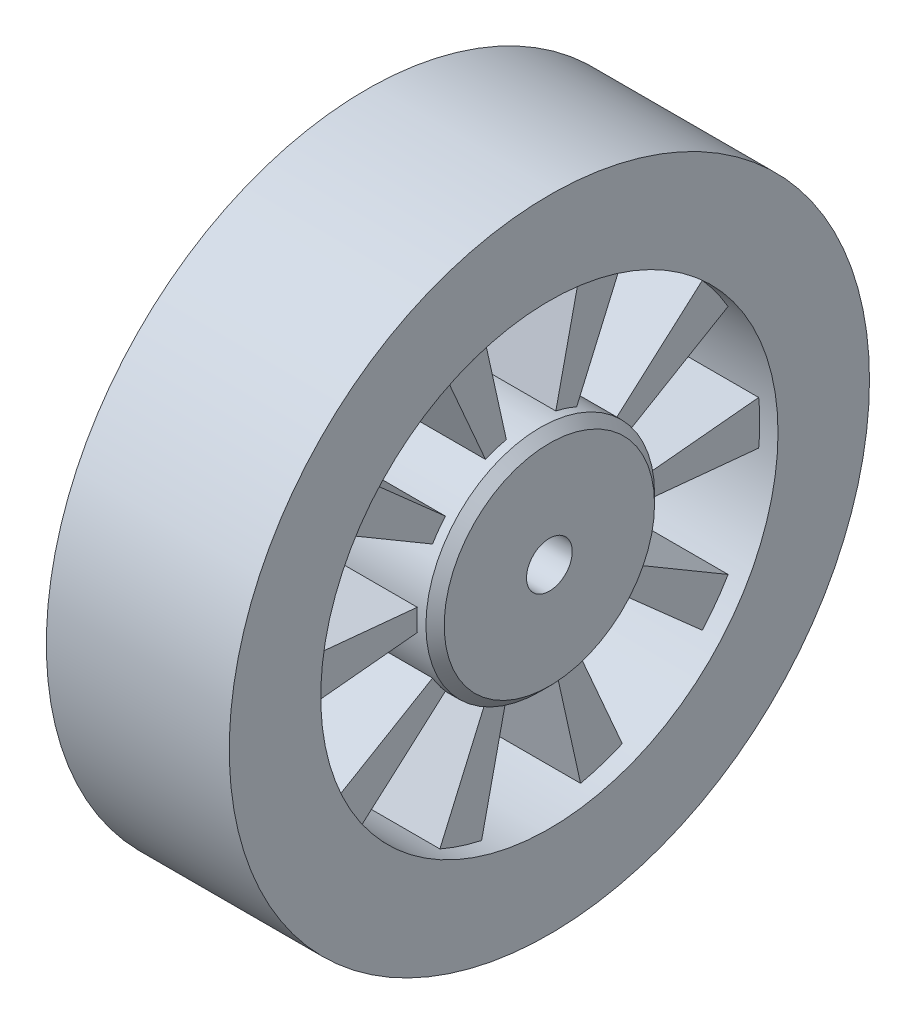
SolidWorks part; units mm, degrees
ref_plane "Front Plane" through (0, 0, 0) normal (0, 0, 1) x (1, 0, 0)
ref_plane "Top Plane" through (0, 0, 0) normal (0, 1, 0) x (1, 0, 0)
ref_plane "Right Plane" through (0, 0, 0) normal (1, 0, 0) x (0, 0, -1)
sketch "Sketch1" plane through (0, 0, 0) normal (1, 0, 0) x (0, 0, -1)
  circle A0 centre (0, 0) radius 3.175
  circle A1 centre (0, 0) radius 44.45
  dimension "D1" = 6.35
  dimension "D2" = 88.9
extrude "Boss-Extrude1" add sketch "Sketch1" along normal blind 25.4
sketch "Sketch2" plane through (25.4, 0, 0) normal (1, 0, 0) x (0, 0, -1)
  circle A0 centre (0, 0) radius 31.75
  circle A1 centre (0, 0) radius 44.45 construction
  circle A2 centre (0, 0) radius 15.875
  circle A3 centre (0, 0) radius 3.175 construction
  dimension "D1" = 12.7
  dimension "D2" = 12.7
extrude "Cut-Extrude1" cut sketch "Sketch2" against normal blind 2.54
sketch "Sketch3" plane through (22.86, 0, 0) normal (1, 0, 0) x (0, 0, -1)
  line L0 (0, 0) -> (0, 10.9166) construction
  line L1 (3.436, 15.4987) -> (6.872, 30.9974)
  line L2 (-3.436, 15.4987) -> (-6.872, 30.9974)
  line L3 (6.3301, 14.5583) -> (12.6603, 29.1167)
  line L4 (11.8897, 10.5191) -> (23.7793, 21.0382)
  line L5 (13.6784, 8.0572) -> (27.3567, 16.1143)
  line L6 (15.8019, 1.5216) -> (31.6038, 3.0431)
  line L7 (15.8019, -1.5216) -> (31.6038, -3.0431)
  line L8 (13.6784, -8.0572) -> (27.3567, -16.1143)
  line L9 (11.8897, -10.5191) -> (23.7793, -21.0382)
  line L10 (6.3301, -14.5583) -> (12.6603, -29.1167)
  line L11 (3.436, -15.4987) -> (6.872, -30.9974)
  line L12 (-3.436, -15.4987) -> (-6.872, -30.9974)
  line L13 (-6.3301, -14.5583) -> (-12.6603, -29.1167)
  line L14 (-11.8897, -10.5191) -> (-23.7793, -21.0382)
  line L15 (-13.6784, -8.0572) -> (-27.3567, -16.1143)
  line L16 (-15.8019, -1.5216) -> (-31.6038, -3.0431)
  line L17 (-15.8019, 1.5216) -> (-31.6038, 3.0431)
  line L18 (-13.6784, 8.0572) -> (-27.3567, 16.1143)
  line L19 (-11.8897, 10.5191) -> (-23.7793, 21.0382)
  line L20 (-6.3301, 14.5583) -> (-12.6603, 29.1167)
  circle A0 centre (0, 0) radius 15.875 construction
  circle A1 centre (0, 0) radius 31.75 construction
  arc A2 (3.436, 15.4987) -> (-3.436, 15.4987) centre (0, 0) ccw
  arc A3 (6.872, 30.9974) -> (-6.872, 30.9974) centre (0, 0) ccw
  circle A4 centre (0, 0) radius 31.75 construction
  arc A5 (11.8897, 10.5191) -> (6.3301, 14.5583) centre (0, 0) ccw
  arc A6 (23.7793, 21.0382) -> (12.6603, 29.1167) centre (0, 0) ccw
  arc A7 (15.8019, 1.5216) -> (13.6784, 8.0572) centre (0, 0) ccw
  arc A8 (31.6038, 3.0431) -> (27.3567, 16.1143) centre (0, 0) ccw
  arc A9 (13.6784, -8.0572) -> (15.8019, -1.5216) centre (0, 0) ccw
  arc A10 (27.3567, -16.1143) -> (31.6038, -3.0431) centre (0, 0) ccw
  arc A11 (6.3301, -14.5583) -> (11.8897, -10.5191) centre (0, 0) ccw
  arc A12 (12.6603, -29.1167) -> (23.7793, -21.0382) centre (0, 0) ccw
  arc A13 (-3.436, -15.4987) -> (3.436, -15.4987) centre (0, 0) ccw
  arc A14 (-6.872, -30.9974) -> (6.872, -30.9974) centre (0, 0) ccw
  arc A15 (-11.8897, -10.5191) -> (-6.3301, -14.5583) centre (0, 0) ccw
  arc A16 (-23.7793, -21.0382) -> (-12.6603, -29.1167) centre (0, 0) ccw
  arc A17 (-15.8019, -1.5216) -> (-13.6784, -8.0572) centre (0, 0) ccw
  arc A18 (-31.6038, -3.0431) -> (-27.3567, -16.1143) centre (0, 0) ccw
  arc A19 (-13.6784, 8.0572) -> (-15.8019, 1.5216) centre (0, 0) ccw
  arc A20 (-27.3567, 16.1143) -> (-31.6038, 3.0431) centre (0, 0) ccw
  arc A21 (-6.3301, 14.5583) -> (-11.8897, 10.5191) centre (0, 0) ccw
  arc A22 (-12.6603, 29.1167) -> (-23.7793, 21.0382) centre (0, 0) ccw
  point P82 (0, 0)
  dimension "D1" = 25
  dimension "D2" = 10
extrude "Cut-Extrude2" cut sketch "Sketch3" against normal through all both and the other way through all
chamfer "Chamfer1" distance 1.27 angle 45 1 edges at (25.4, 0, -15.875)
